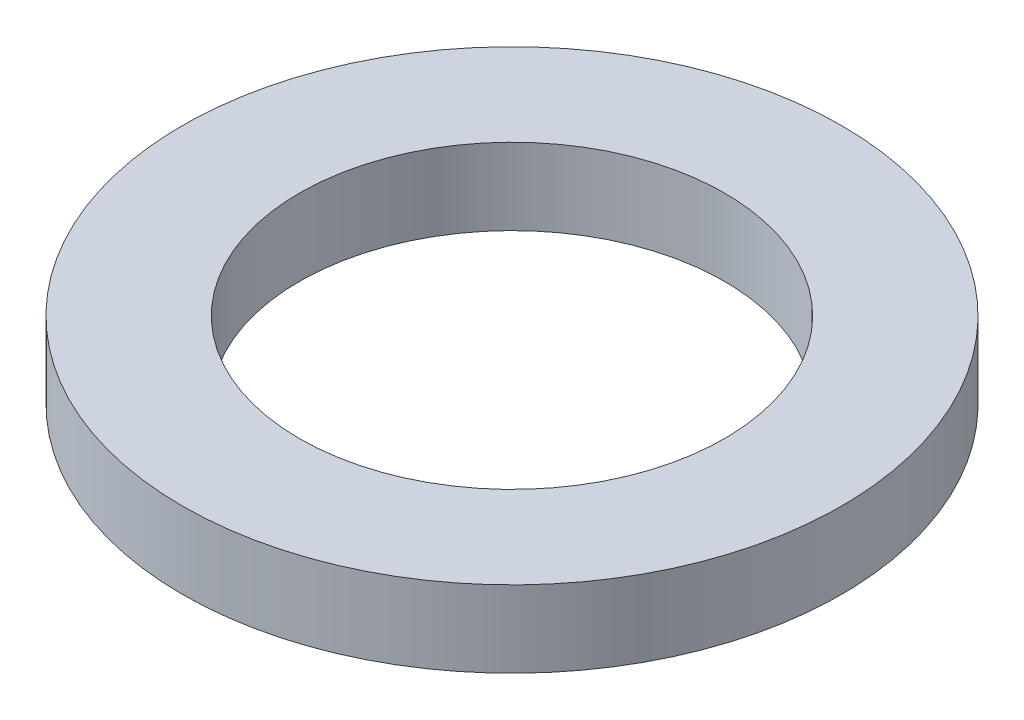
SolidWorks part; units mm, degrees
ref_plane "Front Plane" through (0, 0, 0) normal (0, 0, 1) x (1, 0, 0)
ref_plane "Top Plane" through (0, 0, 0) normal (0, 1, 0) x (1, 0, 0)
ref_plane "Right Plane" through (0, 0, 0) normal (1, 0, 0) x (0, 0, -1)
sketch "Sketch1" plane through (0, 0, 0) normal (0, 1, 0) x (1, 0, 0)
  circle A0 centre (0, 0) radius 77.5
  dimension "FLANGE_OD" = 155
extrude "Boss-Extrude1" add sketch "Sketch1" along normal blind 18
sketch "Sketch2" plane through (0, 0, 0) normal (0, 1, 0) x (1, 0, 0)
  circle A0 centre (0, 0) radius 50
  dimension "BORE_D" = 100
extrude "Cut-Extrude1" cut sketch "Sketch2" along normal through all
sketch "Sketch3" plane through (0, 18, 0) normal (0, 1, 0) x (1, 0, 0)
  circle A0 centre (0, 0) radius 27.9761 construction
  circle A1 centre (-27.9761, 0) radius 2.9096
  dimension "BOLT_D" = 5.8192
  dimension "BOLT_PCD" = 55.9522
extrude "Cut-Extrude2" cut sketch "Sketch3" against normal blind 15.842 rebuild error yes
pattern_circular "CirPattern1" count 3 over 360 rebuild error yes
